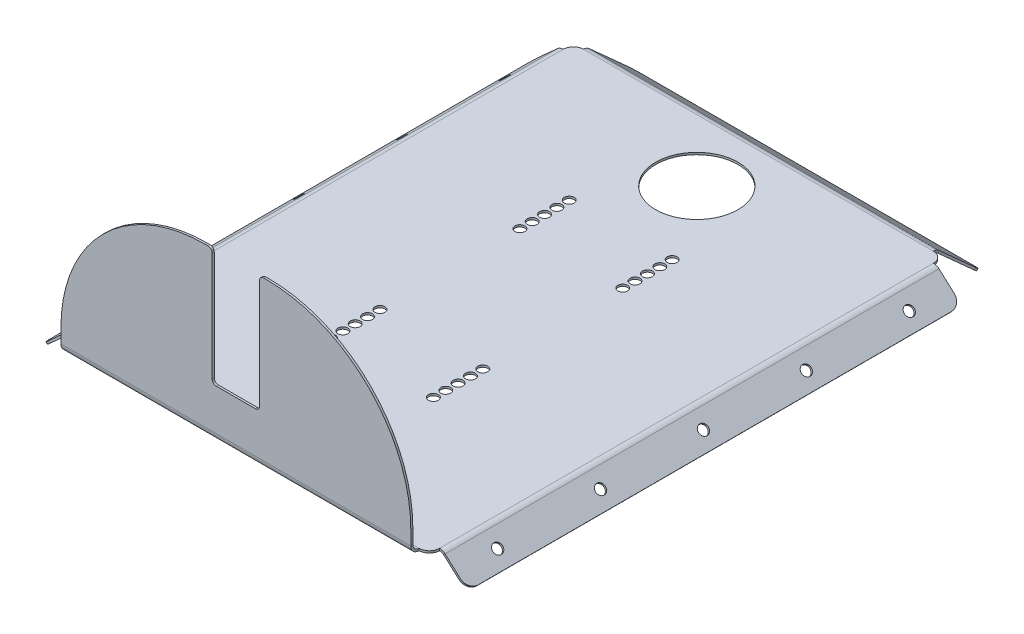
SolidWorks part; units mm, degrees
note: The reader was unsure of these and kept them because the rebuilt part matched: flange length of "Aresta-Flange1", "Aresta-Flange2", "Aresta-Flange3".
ref_plane "Plano frontal" through (0, 0, 0) normal (0, 0, 1) x (1, 0, 0)
ref_plane "Plano superior" through (0, 0, 0) normal (0, 1, 0) x (1, 0, 0)
ref_plane "Plano direito" through (0, 0, 0) normal (1, 0, 0) x (0, 0, -1)
sketch "Esboço1" plane through (0, 0, 0) normal (0, 1, 0) x (1, 0, 0)
  line L1 (-90, 125) -> (90, 125)
  line L2 (-90, 125) -> (-90, -125)
  line L3 (-90, -125) -> (90, -125)
  line L4 (90, 125) -> (90, -125)
  line L5 (-90, 125) -> (90, -125) construction
  line L6 (-90, -125) -> (90, 125) construction
  point P0 (0, 0)
  dimension "D1" = 250
  dimension "D2" = 180
base flange "Flange-base1" sketch "Esboço1" thickness 1 reverse thickness direction no parameters "D1"=3
sketch "Esboço6" plane through (0, 0, 0) normal (0, 1, 0) x (1, 0, 0)
  line L0 (-25, 46) -> (-25, -46) construction
  line L1 (0, -125) -> (0, 125) construction
  line L2 (-90, -125) -> (90, -125) construction
  line L3 (90, 125) -> (-90, 125) construction
  line L4 (-25, 46) -> (-25, 40) construction
  line L7 (-25, 46) -> (25, 46) construction
  line L8 (-25, -46) -> (25, -46) construction
  line L9 (25, 46) -> (25, -46) construction
  line L10 (-25, -46) -> (25, 46) construction
  line L11 (-25, 46) -> (25, -46) construction
  circle A0 centre (-25, 52) radius 2.4
  circle A1 centre (25, 52) radius 2.4
  circle A2 centre (-25, -40) radius 2.4
  circle A3 centre (25, -40) radius 2.4
  circle A4 centre (-25, -46) radius 2.4
  circle A5 centre (25, -46) radius 2.4
  circle A6 centre (-25, 46) radius 2.4
  circle A7 centre (25, 46) radius 2.4
  circle A8 centre (-25, 58) radius 2.4
  circle A9 centre (25, 58) radius 2.4
  circle A10 centre (-25, -34) radius 2.4
  circle A11 centre (25, -34) radius 2.4
  circle A12 centre (-25, 40) radius 2.4
  circle A13 centre (25, 40) radius 2.4
  circle A14 centre (-25, -52) radius 2.4
  circle A15 centre (25, -52) radius 2.4
  circle A16 centre (-25, 34) radius 2.4
  circle A17 centre (25, 34) radius 2.4
  circle A18 centre (-25, -58) radius 2.4
  circle A19 centre (25, -58) radius 2.4
  circle A20 centre (0, 95) radius 20
  circle A21 centre (-25, -22) radius 2.4 [skipped]
  circle A22 centre (-25, -28) radius 2.4 [skipped]
  circle A23 centre (25, -22) radius 2.4 [skipped]
  circle A24 centre (25, -28) radius 2.4 [skipped]
  circle A25 centre (-25, 70) radius 2.4 [skipped]
  circle A26 centre (-25, 64) radius 2.4 [skipped]
  circle A27 centre (25, 70) radius 2.4 [skipped]
  circle A28 centre (25, 64) radius 2.4 [skipped]
  point P0 (0, 0)
  dimension "D3" = 40
  dimension "D2" = 30
  dimension "D5" = 6
  dimension "D1" = 5
  dimension "D4" = 3
extrude "Corte-extrusão1" cut sketch "Esboço6" against normal blind 10 normal cut yes
fillet "Filete1" radius 5 4 edges at (90, -0.5, -125) (-90, -0.5, -125) (-90, -0.5, 125) (90, -0.5, 125)
edge flange "Aresta-Flange1" sketch "Esboço13" flange angle 138 flange length 30 flange position bend outside bend radius 3 thickness 1 relief rectangular parameters "D6"=10
sketch "Esboço13" plane through (0, -1, -125) normal (0, 0.7431, -0.6691) x (1, 0, 0)
  line L2 (-85, 0) -> (-85, 30)
  line L3 (-85, 30) -> (85, 30)
  line L4 (85, 30) -> (85, 0)
  line L5 (85, 0) -> (-85, 0) construction
  line L6 (85, 0) -> (-85, 0)
bend "DobradeAresta1" bend radius 3 bend angle 42 parameters "D5"=1
edge flange "Aresta-Flange2" sketch "Esboço20" flange profiles "Esboço20", "Esboço21" flange angle 138 flange length 16.05 flange position bend outside bend radius 3 thickness 1 relief rectangular parameters "D6"=10, "D8"=1
sketch "Esboço20" plane through (90, -1, 0) normal (0.6691, 0.7431, 0) x (0, 0, 1)
  line L2 (-120, 0) -> (-120, 16.05)
  line L3 (-120, 16.05) -> (120, 16.05)
  line L4 (120, 16.05) -> (120, 0)
  line L5 (120, 0) -> (-120, 0) construction
  line L6 (120, 0) -> (-120, 0)
sketch "Esboço21" plane through (-90, -1, 0) normal (-0.6691, 0.7431, 0) x (0, 0, -1)
  line L2 (-120, 0) -> (-120, 16.05)
  line L3 (-120, 16.05) -> (120, 16.05)
  line L4 (120, 16.05) -> (120, 0)
  line L5 (120, 0) -> (-120, 0) construction
  line L6 (120, 0) -> (-120, 0)
bend "DobradeAresta2" bend radius 3 bend angle 42 parameters "D5"=2
bend "DobradeAresta3" bend radius 3 bend angle 42 parameters "D5"=3
fillet "Filete2" radius 5 6 edges at (-103.4136, -11.368, 120) (-85, -20.7023, -148.7805) (-103.4136, -11.368, -120) (85, -20.7023, -148.7805) (103.4136, -11.368, -120) (103.4136, -11.368, 120)
edge flange "Aresta-Flange3" sketch "Esboço26" flange angle 90 flange length 80 flange position bend outside bend radius 3 thickness 1 relief rectangular parameters "D6"=10
sketch "Esboço26" plane through (0, 0, 125) normal (0, 0, 1) x (1, 0, 0)
  line L0 (-85, 0) -> (85, 0) construction
  line L1 (-85, 0) -> (85, 0)
  line L2 (-85, 0) -> (-85, 80)
  line L3 (-85, 80) -> (85, 80)
  line L4 (85, 80) -> (85, 0)
bend "DobradeAresta4" bend radius 3 bend angle 90 parameters "D5"=4
fillet "Filete3" radius 70 2 edges at (-85, 80, 128.5) (85, 80, 128.5)
sketch "Esboço29" plane through (0, 0, 129) normal (0, 0, 1) x (1, 0, 0)
  line L0 (0, 0) -> (0, 80) construction
  line L1 (15, 80) -> (-15, 80) construction
  line L2 (85, 3) -> (-85, 3) construction
  line L3 (-11.5, 23) -> (11.5, 23)
  line L4 (-11.5, 23) -> (-11.5, 80)
  line L5 (-11.5, 80) -> (11.5, 80)
  line L6 (11.5, 23) -> (11.5, 80)
  line L7 (-11.5, 23) -> (11.5, 80) construction
  line L8 (-11.5, 80) -> (11.5, 23) construction
  point P5 (0, 51.5)
  dimension "D1" = 23
  dimension "D2" = 20
extrude "Corte-extrusão2" cut sketch "Esboço29" against normal through all normal cut yes
fillet "Filete4" radius 2 4 edges at (11.5, 23, 128.5) (-11.5, 23, 128.5) (11.5, 80, 128.5) (-11.5, 80, 128.5)
sketch "Esboço32" plane through (40.9837, 45.517, 0) normal (0.6691, 0.7431, 0) x (0.7431, -0.6691, 0)
  line L0 (77.0088, -100) -> (77.0088, 100) construction
  line L1 (84.458, 0) -> (69.5596, 0) construction
  line L2 (69.5596, -120) -> (69.5596, 120) construction
  line L3 (84.458, -115) -> (84.458, 115) construction
  circle A0 centre (77.0088, 0) radius 2.4
  circle A1 centre (77.0088, -100) radius 2.4
  circle A2 centre (77.0088, -50) radius 2.4
  circle A3 centre (77.0088, 50) radius 2.4
  circle A4 centre (77.0088, 100) radius 2.4
  dimension "D1" = 50
  dimension "D2" = 50
  dimension "D3" = 50
  dimension "D4" = 50
extrude "Corte-extrusão3" cut sketch "Esboço32" against normal up to next normal cut yes
mirror "Espelhar1" about plane through (0, 0, 0) normal (1, 0, 0) of "Corte-extrusão3"
sketch "Curva-Linhas1" plane through (0, 0, 0) normal (0, 1, 0) x (1, 0, 0)
sketch "Caixa delimitadora1" plane through (0, 0, 0) normal (0, 1, 0) x (1, 0, 0)
sheet metal parameters "Chapa metálica(1)" thickness 1 parameters "D1"=3
flat pattern "Padrão-Plano(1)" [suppressed]
sketch "Curva-Linhas2" plane through (0, 0, 0) normal (0, 1, 0) x (1, 0, 0)
sketch "Caixa delimitadora2" [suppressed] plane through (0, 0, 0) normal (0, 1, 0) x (1, 0, 0)
sheet metal parameters "Chapa metálica(2)" thickness 1 parameters "D1"=3
flat pattern "Padrão-Plano(1)"
sketch "Curva-Linhas3" plane through (0, 0, 0) normal (0, 1, 0) x (1, 0, 0)
sketch "Caixa delimitadora3" [suppressed] plane through (0, 0, 0) normal (0, 1, 0) x (1, 0, 0)
sheet metal parameters "Chapa metálica(4)" thickness 1 parameters "D1"=3
flat pattern "Padrão-Plano(1)" [suppressed]
sketch "Curva-Linhas5" plane through (0, 0, 0) normal (0, 1, 0) x (1, 0, 0)
sketch "Caixa delimitadora5" [suppressed] plane through (0, 0, 0) normal (0, 1, 0) x (1, 0, 0)
bend of the flat pattern "Planificar-<DobradeAresta1>1"
sheet metal parameters "Chapa metálica(5)" thickness 1 parameters "D1"=3
flat pattern "Padrão-Plano(1)" [suppressed]
sketch "Curva-Linhas6" plane through (0, 0, 0) normal (0, 1, 0) x (1, 0, 0)
sketch "Caixa delimitadora6" [suppressed] plane through (0, 0, 0) normal (0, 1, 0) x (1, 0, 0)
bend of the flat pattern "Planificar-<DobradeAresta1>2"
bend of the flat pattern "Planificar-<DobradeAresta2>1"
bend of the flat pattern "Planificar-<DobradeAresta3>1"
sheet metal parameters "Chapa metálica(6)" thickness 1 parameters "D1"=3
flat pattern "Padrão-Plano(1)" [suppressed]
sketch "Curva-Linhas7" plane through (0, 0, 0) normal (0, 1, 0) x (1, 0, 0)
sketch "Caixa delimitadora7" [suppressed] plane through (0, 0, 0) normal (0, 1, 0) x (1, 0, 0)
bend of the flat pattern "Planificar-<DobradeAresta1>3"
bend of the flat pattern "Planificar-<DobradeAresta2>2"
bend of the flat pattern "Planificar-<DobradeAresta3>2"
bend of the flat pattern "Planificar-<DobradeAresta4>1"
sheet metal parameters "Chapa metálica(7)" thickness 1 parameters "D1"=3
flat pattern "Padrão-Plano(1)" [suppressed]
sketch "Curva-Linhas8" plane through (0, 0, 0) normal (0, 1, 0) x (1, 0, 0)
sketch "Caixa delimitadora8" [suppressed] plane through (0, 0, 0) normal (0, 1, 0) x (1, 0, 0)
bend of the flat pattern "Planificar-<DobradeAresta1>4"
bend of the flat pattern "Planificar-<DobradeAresta2>3"
bend of the flat pattern "Planificar-<DobradeAresta3>3"
bend of the flat pattern "Planificar-<DobradeAresta4>2"
sheet metal parameters "Chapa metálica(8)" thickness 1 parameters "D1"=3
flat pattern "Padrão-Plano(1)" [suppressed]
sketch "Curva-Linhas9" plane through (0, 0, 0) normal (0, 1, 0) x (1, 0, 0)
sketch "Caixa delimitadora9" [suppressed] plane through (0, 0, 0) normal (0, 1, 0) x (1, 0, 0)
bend of the flat pattern "Planificar-<DobradeAresta1>5"
bend of the flat pattern "Planificar-<DobradeAresta2>4"
bend of the flat pattern "Planificar-<DobradeAresta3>4"
bend of the flat pattern "Planificar-<DobradeAresta4>3"
sheet metal parameters "Chapa metálica(9)" thickness 1 parameters "D1"=3
flat pattern "Padrão-Plano(1)" [suppressed]
sketch "Curva-Linhas10" plane through (0, 0, 0) normal (0, 1, 0) x (1, 0, 0)
sketch "Caixa delimitadora10" [suppressed] plane through (0, 0, 0) normal (0, 1, 0) x (1, 0, 0)
bend of the flat pattern "Planificar-<DobradeAresta1>6"
bend of the flat pattern "Planificar-<DobradeAresta2>5"
bend of the flat pattern "Planificar-<DobradeAresta3>5"
bend of the flat pattern "Planificar-<DobradeAresta4>4"
